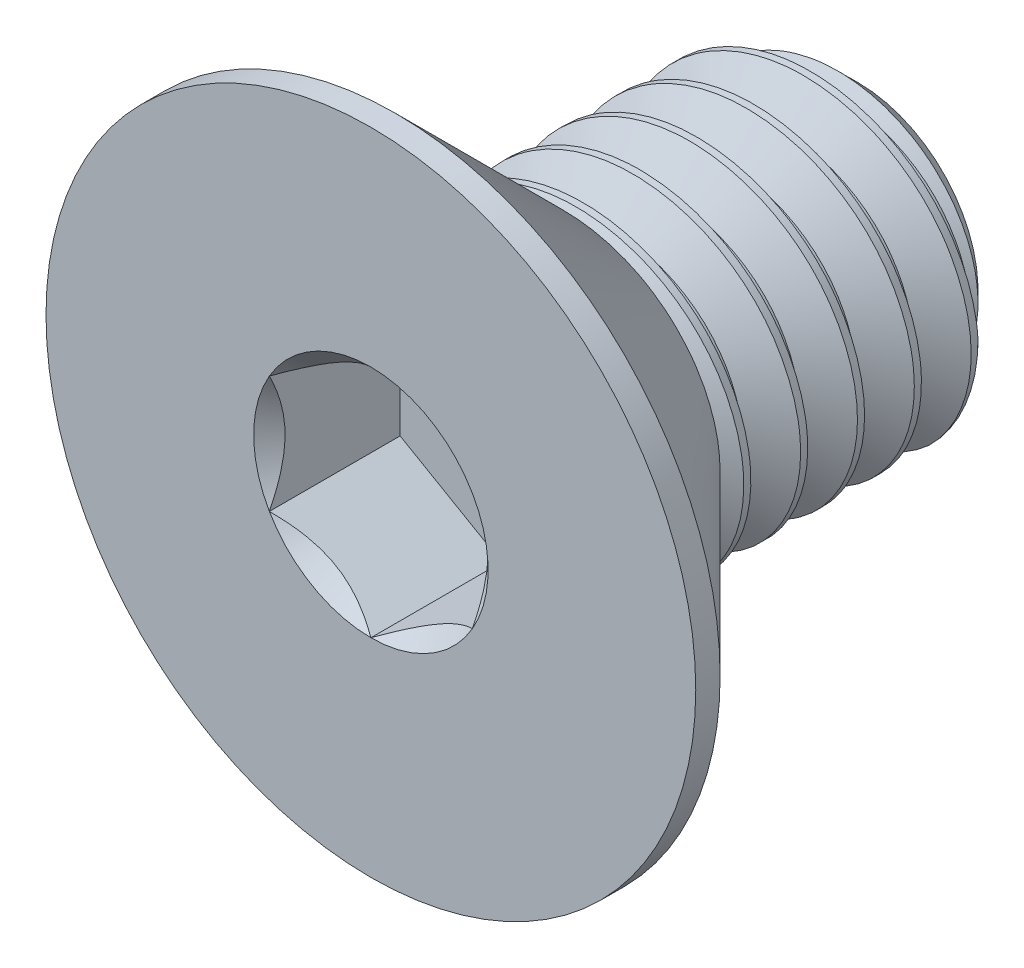
SolidWorks part; units mm, degrees
ref_plane "Front" through (0, 0, 0) normal (0, 0, 1) x (1, 0, 0)
ref_plane "Top" through (0, 0, 0) normal (0, 1, 0) x (1, 0, 0)
ref_plane "Right" through (0, 0, 0) normal (1, 0, 0) x (0, 0, -1)
sketch "Sketch1" plane through (0, 0, 0) normal (1, 0, 0) x (0, 0, -1)
  line L0 (0, 4) -> (0.3, 4) construction
  line L1 (0.3, 4) -> (2.3, 2) construction
  line L2 (0, 2) -> (6, 2)
  line L3 (6, 2) -> (6, 0)
  line L4 (6, 0) -> (0, 0)
  line L5 (0, 0) -> (0, 4) construction
  line L6 (0, 4) -> (0, -4) construction
  line L7 (6, 2) -> (6, -2) construction
  line L8 (0, -4) -> (0.3, -4) construction
  line L9 (0.3, -4) -> (2.3, -2) construction
  line L11 (0, 2) -> (0, 0)
  line L12 (2.3, 2) -> (2.3, 0) construction
  dimension "Head Ht" = 2.3
  dimension "Head Dia" = 8
  dimension "Dia" = 4
  dimension "Lg" = 6
  dimension "Head Angle" = 90
revolve "Revolve1" add sketch "Sketch1" angle 360 mid plane about L4
sketch "Sketch3" plane through (0, 0, -6) normal (0, 0, -1) x (-1, 0, 0)
  circle A0 centre (0, 0) radius 2
curve "Helix/Spiral1" pitch 0.7 height 6 radius 2 centre (0, 0, -6) axis (0, 0, 1) start towards (0, 1, 0)
sketch "Sketch2" plane through (0, 0, 0) normal (1, 0, 0) x (0, 0, -1)
  line L0 (6, 2) -> (6.6125, 2)
  line L1 (6.6125, 2) -> (6.35, 1.5453)
  line L2 (6.35, 1.5453) -> (6.2625, 1.5453)
  line L3 (6.2625, 1.5453) -> (6, 2)
  line L4 (6.1312, 1.7727) -> (6.4812, 1.7727) construction
  dimension "D1" = 60
  dimension "D2" = 0.0875
  dimension "D3" = 0.35
chamfer "Chamfer1" distance 0.525 angle 45 1 edges at (0, 2, -6)
sweep "Cut-Sweep1" cut profiles "Sketch2" path "Helix/Spiral1" align with end faces yes
sketch "Sketch7" plane through (0, 0, 0) normal (1, 0, 0) x (0, 0, -1)
  line L0 (0, 4) -> (0.3, 4) construction
  line L1 (0.3, 4) -> (2.3, 2) construction
  line L2 (0, 4) -> (0.3, 4)
  line L3 (0.3, 4) -> (2.3, 2)
  line L4 (2.3, 2) -> (2.3, 0) construction
  line L5 (2.3, 2) -> (2.3, 0)
  line L7 (0, 0) -> (0, 4) construction
  line L8 (0, 0) -> (0, 4)
  line L9 (0, 0) -> (2.3, 0)
  line L10 (4.4, 0) -> (-4.4, 0) construction
revolve "Revolve2" add sketch "Sketch7" angle 360 mid plane about L9
ref_plane "Plane1" through (0, 0, -2.3) normal (0, 0, 1) x (1, 0, 0)
sketch "Sketch8" plane through (0, 0, -2.3) normal (0, 0, 1) x (1, 0, 0)
  circle A0 centre (0, 0) radius 2
extrude "Boss-Extrude1" add sketch "Sketch8" against normal through all draft 45
sketch "Sketch5" plane through (0, 0, 0) normal (0, 0, 1) x (1, 0, 0)
  line L1 (1.25, -0.7217) -> (1.25, 0.7217)
  line L2 (1.25, 0.7217) -> (0, 1.4434)
  line L3 (0, 1.4434) -> (-1.25, 0.7217)
  line L4 (-1.25, 0.7217) -> (-1.25, -0.7217)
  line L5 (-1.25, -0.7217) -> (0, -1.4434)
  line L6 (0, -1.4434) -> (1.25, -0.7217)
  circle A0 centre (0, 0) radius 1.25 construction
  dimension "Hex" = 2.5
extrude "Cut-Extrude2" cut sketch "Sketch5" against normal blind 1.61
sketch "Sketch6" plane through (0, 0, 0) normal (0, 0, 1) x (1, 0, 0)
  circle A0 centre (0, 0) radius 1.4434
extrude "Cut-Extrude3" cut sketch "Sketch6" against normal blind 1.61 draft 45
sketch "Sketch9" [suppressed] plane through (0, 0, -1.5) normal (0, 0, 1) x (1, 0, 0)
  circle A1 centre (0, 0) radius 1.25
  circle A2 centre (0, 0) radius 1.25
  point P0 (0, 1.25)
  dimension "D1" = 0
extrude "Boss-Extrude2" [suppressed] add sketch "Sketch9" against normal offset from surface (3.5 mm away) 26 up to face at (0, 1.475, -6)
fillet "Fillet1" [suppressed] radius 0.4
sketch "Sketch10" plane through (0, 0, 0) normal (1, 0, 0) x (0, 0, -1)
  line L0 (6, 2) -> (6, -2) construction
  point P0 (4.95, -2)
  dimension "D1" = 1.05
equation "\"D3@Helix/Spiral1\" = \"Lg@Sketch1\""
equation "\"D2@Sketch2\" = \"D4@Helix/Spiral1\" * .125"
equation "\"D3@Sketch2\" = \"D4@Helix/Spiral1\" * .5"
equation "\"D1@Chamfer1\" = \"D4@Helix/Spiral1\" * .75"
equation "\"D1@Cut-Extrude2\" = \"Head Ht@Sketch1\" * .7"
equation "\"D1@Sketch10\" = \"D4@Helix/Spiral1\" * 1.5"
equation "\"D1@Cut-Extrude3\" = \"D1@Cut-Extrude2\""
equation "\"D1@Fillet1\" = \"Dia@Sketch1\" * .1"
